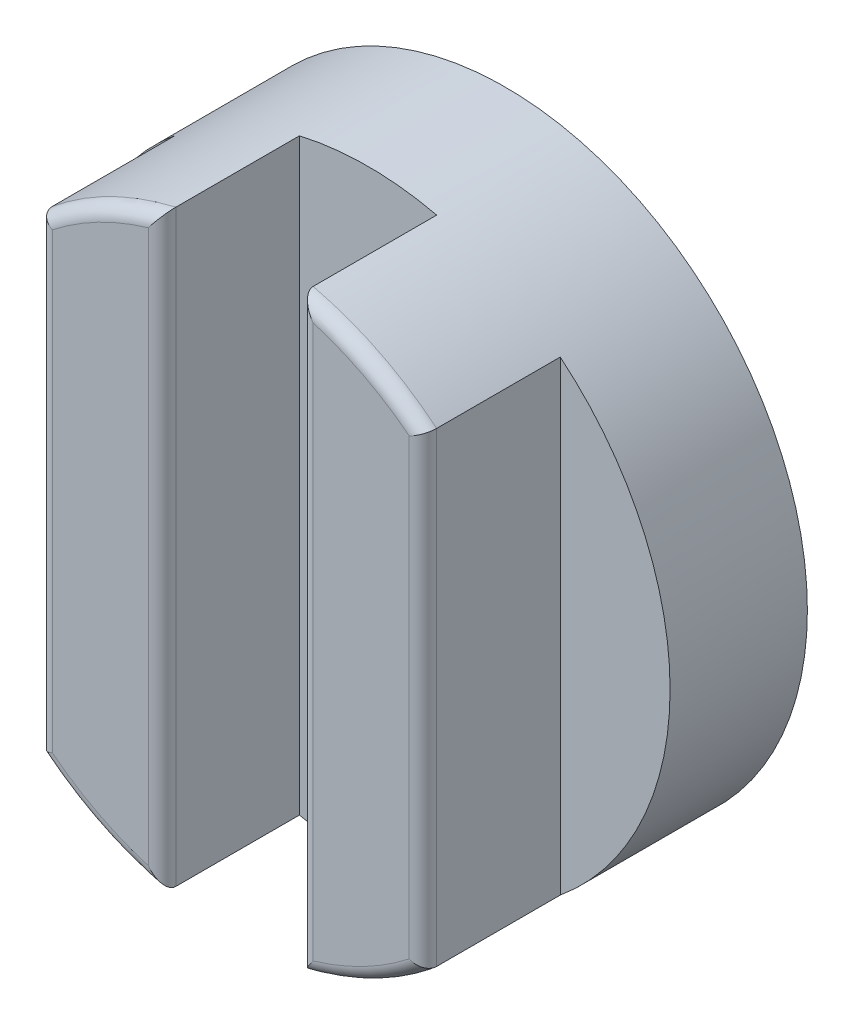
SolidWorks part; units mm, degrees
ref_plane "Plan de face" through (0, 0, 0) normal (0, 0, 1) x (1, 0, 0)
ref_plane "Plan de dessus" through (0, 0, 0) normal (0, 1, 0) x (1, 0, 0)
ref_plane "Plan de droite" through (0, 0, 0) normal (1, 0, 0) x (0, 0, -1)
sketch "Esquisse1" plane through (0, 0, 0) normal (0, 0, 1) x (1, 0, 0)
  circle A0 centre (0, 0) radius 11
  dimension "D1" = 22
extrude "Boss.-Extru.1" add sketch "Esquisse1" along normal blind 5
sketch "Esquisse2" plane through (0, 0, 5) normal (0, 0, 1) x (1, 0, 0)
  line L0 (0, 5.7045) -> (0, -6.8994) construction
  line L1 (-7, 8.4853) -> (-7, -8.4853)
  line L2 (-2.5, 10.7121) -> (-2.5, -10.7121)
  line L3 (7, 8.4853) -> (7, -8.4853)
  line L4 (2.5, 10.7121) -> (2.5, -10.7121)
  circle A0 centre (0, 0) radius 11 construction
  arc A1 (-2.5, -10.7121) -> (2.5, -10.7121) centre (0, 0) ccw
  arc A2 (2.5, 10.7121) -> (-2.5, 10.7121) centre (0, 0) ccw
  circle A3 centre (0, 0) radius 11
  circle M1 centre (0, 0) radius 11
  dimension "D1" = 5
  dimension "D2" = 4.5
extrude "Boss.-Extru.3" add sketch "Esquisse2" along normal blind 5 contours L2 L1 M1 | L4 L3 M1 region at (-4.6661, 0, 5) region at (4.6661, 0, 5)
fillet "Congé3" radius 0.5 8 edges at (4.8788, 9.8589, 10) (7, 0, 10) (2.5, 0, 10) (4.8788, -9.8589, 10) (-4.8788, -9.8589, 10) (-2.5, 0, 10) (-4.8788, 9.8589, 10) (-7, 0, 10)
